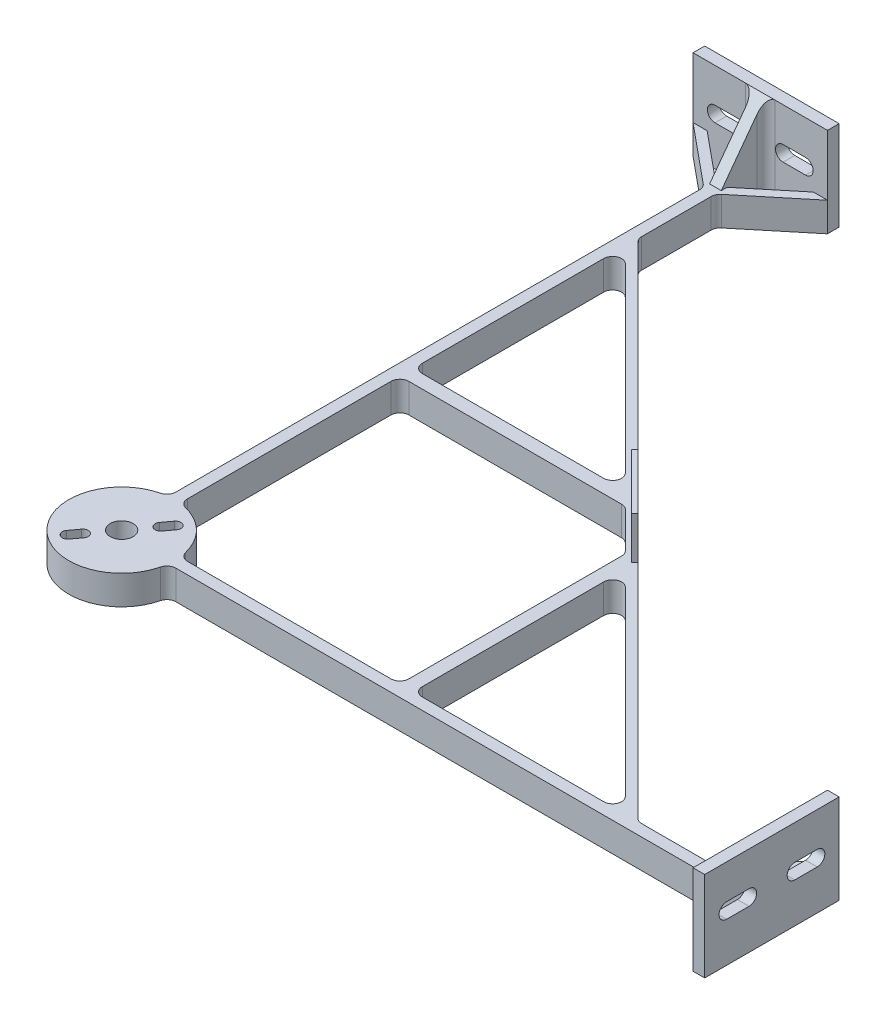
SolidWorks part; units mm, degrees
ref_plane "Front Plane" through (0, 0, 0) normal (0, 0, 1) x (1, 0, 0)
ref_plane "Top Plane" through (0, 0, 0) normal (0, 1, 0) x (1, 0, 0)
ref_plane "Right Plane" through (0, 0, 0) normal (1, 0, 0) x (0, 0, -1)
sketch "Sketch1" plane through (0, 0, 0) normal (0, 1, 0) x (1, 0, 0)
  line L0 (1.651, 14.8948) -> (1.651, 77.2021)
  line L1 (0, 0) -> (0, 189.2633) construction
  line L2 (-1.651, 14.8948) -> (-1.651, 180.975)
  line L3 (-1.651, 180.975) -> (1.651, 180.975)
  line L4 (-12.33, -16.663) -> (12.0176, 16.2408) construction
  line L5 (14.8948, -1.651) -> (180.975, -1.651)
  line L6 (4.6836, 6.3296) -> (6.4967, 8.7797) construction
  line L7 (3.4586, 7.2361) -> (5.2716, 9.6862)
  line L8 (180.975, -1.651) -> (180.975, 1.651)
  line L9 (14.8948, 1.651) -> (141.0789, 1.651)
  line L10 (5.9087, 5.4231) -> (7.7217, 7.8732)
  line L11 (0, 0) -> (16.238, -12.0155) construction
  line L12 (-4.6836, -6.3296) -> (-6.4967, -8.7797) construction
  line L13 (-5.9087, -5.4231) -> (-7.7217, -7.8732)
  line L14 (-3.4586, -7.2361) -> (-5.2716, -9.6862)
  line L15 (-1.651, 14.8948) -> (14.8948, -1.651) construction
  line L16 (1.651, 141.0789) -> (61.7178, 81.0121)
  line L17 (144.6711, 1.651) -> (1.651, 144.6711)
  line L18 (144.6711, 1.651) -> (166.629, 1.651)
  line L19 (141.0789, 1.651) -> (144.6711, 1.651) construction
  line L20 (1.651, 144.6711) -> (1.651, 180.975)
  line L21 (1.651, 81.0121) -> (61.7178, 81.0121)
  line L22 (1.651, 77.2021) -> (65.5278, 77.2021)
  line L23 (0, 0) -> (69.7604, 69.7604) construction
  line L24 (77.2021, 1.651) -> (77.2021, 65.5278)
  line L25 (81.0121, 1.651) -> (81.0121, 61.7178)
  line L26 (81.0121, 61.7178) -> (141.0789, 1.651)
  line L27 (65.5278, 77.2021) -> (77.2021, 65.5278)
  line L28 (1.651, 81.0121) -> (1.651, 141.0789)
  line L29 (169.921, 1.651) -> (180.975, 15.0573)
  line L30 (180.975, 15.0573) -> (180.975, 19.05)
  line L31 (180.975, 19.05) -> (166.629, 1.651)
  line L32 (166.4345, 0) -> (201.9953, 0) construction
  line L33 (180.975, -19.05) -> (166.629, -1.651)
  line L34 (180.975, -15.0573) -> (180.975, -19.05)
  line L35 (169.921, -1.651) -> (180.975, -15.0573)
  line L36 (169.921, 1.651) -> (180.975, 1.651)
  line L37 (166.629, 1.651) -> (169.921, 1.651) construction
  line L38 (-15.0573, 180.975) -> (-19.05, 180.975)
  line L39 (-19.05, 180.975) -> (-1.651, 166.629)
  line L40 (-1.651, 169.921) -> (-15.0573, 180.975)
  line L41 (1.651, 169.921) -> (15.0573, 180.975)
  line L42 (15.0573, 180.975) -> (19.05, 180.975)
  line L43 (19.05, 180.975) -> (1.651, 166.629)
  arc A0 (14.8948, 1.651) -> (1.651, 14.8948) centre (0, 0) ccw
  circle A1 centre (0, 0) radius 3.2385
  arc A2 (3.4586, 7.2361) -> (5.9087, 5.4231) centre (4.6836, 6.3296) ccw
  arc A3 (7.7217, 7.8732) -> (5.2716, 9.6862) centre (6.4967, 8.7797) ccw
  arc A4 (-5.9087, -5.4231) -> (-3.4586, -7.2361) centre (-4.6836, -6.3296) cw
  arc A5 (-5.2716, -9.6862) -> (-7.7217, -7.8732) centre (-6.4967, -8.7797) cw
  arc A6 (-1.651, 14.8948) -> (14.8948, -1.651) centre (0, 0) ccw
  point P14 (5.5901, 7.5546)
  point P25 (-5.5901, -7.5546)
  point P34 (142.875, 1.651)
  point P53 (168.275, 1.651)
  dimension "D3" = 29.972
  dimension "D1" = 6.477
  dimension "D6" = 1.524
  dimension "D7" = 3.048
  dimension "D2" = 36.5
  dimension "D4" = 3.302
  dimension "D5" = 3.302
  dimension "D8" = 7.874
  dimension "D9" = 2.54
  dimension "D10" = 38.1
  dimension "D11" = 3.81
  dimension "D12" = 16.51
  dimension "D13" = 38.1
  dimension "D14" = 12.7
  dimension "D15" = 2.54
  dimension "D16" = 180.975
  dimension "D17" = 180.975
extrude "Boss-Extrude1" add sketch "Sketch1" along normal blind 8.255 contours L2 A6 L5 L8 L36 L29 L30 L31 L18 L17 L20 L3 L14 A5 L13 A4 L9 A0 L0 L22 L27 L24 L25 L26 L21 L28 L16 A1 A3 L10 A2 L7 | L35 L5 L33 L34 | L2 L40 L38 L39 | L43 L42 L41 L20 region at (1.1203, 0, -90.7619) region at (-9.3955, 0, -174.5894) region at (174.5894, 0, 9.3955) region at (9.3955, 0, -174.5894)
sketch "Sketch3" plane through (0, 0, 0) normal (0, 1, 0) x (1, 0, 0)
  line L0 (0, 0) -> (128.7769, 128.7769) construction
  line L1 (180.975, 19.05) -> (184.277, 19.05)
  line L2 (180.975, 19.05) -> (180.975, -19.05)
  line L3 (180.975, -19.05) -> (184.277, -19.05)
  line L4 (184.277, 19.05) -> (184.277, -19.05)
  line L5 (19.05, 184.277) -> (-19.05, 184.277)
  line L6 (-19.05, 180.975) -> (-19.05, 184.277)
  line L7 (19.05, 180.975) -> (-19.05, 180.975)
  line L8 (19.05, 180.975) -> (19.05, 184.277)
  dimension "D1" = 3.302
extrude "Boss-Extrude3" add sketch "Sketch3" along normal blind 25.4
sketch "Sketch4" plane through (0, 8.255, 0) normal (0, 1, 0) x (1, 0, 0)
  line L0 (65.2584, 81.0637) -> (64.3604, 80.1656)
  line L1 (144.6711, 1.651) -> (1.651, 144.6711) construction
  line L2 (64.3604, 80.1656) -> (80.1656, 64.3604)
  line L3 (80.1656, 64.3604) -> (81.0637, 65.2584)
  line L4 (81.0637, 65.2584) -> (65.2584, 81.0637)
  line L5 (71.365, 71.365) -> (72.263, 72.263) construction
  line L6 (65.5278, 77.2021) -> (77.2021, 65.5278) construction
  dimension "D1" = 22.352
  dimension "D2" = 1.27
extrude "Boss-Extrude4" add sketch "Sketch4" along normal blind 11.938
sketch "Sketch5" plane through (184.277, 0, 0) normal (1, 0, 0) x (0, 0, -1)
  line L0 (-12.827, 13.4726) -> (-6.477, 13.4726) construction
  line L1 (-12.827, 15.6316) -> (-6.477, 15.6316)
  line L2 (-12.827, 11.3136) -> (-6.477, 11.3136)
  line L3 (0, 4.9298) -> (0, 30.0782) construction
  line L4 (12.827, 13.4726) -> (6.477, 13.4726) construction
  line L5 (12.827, 15.6316) -> (6.477, 15.6316)
  line L6 (12.827, 11.3136) -> (6.477, 11.3136)
  arc A0 (-12.827, 15.6316) -> (-12.827, 11.3136) centre (-12.827, 13.4726) ccw
  arc A1 (-6.477, 11.3136) -> (-6.477, 15.6316) centre (-6.477, 13.4726) ccw
  arc A2 (12.827, 15.6316) -> (12.827, 11.3136) centre (12.827, 13.4726) cw
  arc A3 (6.477, 11.3136) -> (6.477, 15.6316) centre (6.477, 13.4726) cw
  point P2 (-9.652, 13.4726)
  point P12 (9.652, 13.4726)
  dimension "D1" = 6.35
  dimension "D2" = 4.318
  dimension "D3" = 9.652
ref_plane "Plane1" through (0, 0, 0) normal (0.7071, 0, 0.7071) x (0.7071, 0, -0.7071)
extrude "Cut-Extrude1" cut sketch "Sketch5" against normal through all
mirror "Mirror1" about plane through (0, 0, 0) normal (0.7071, 0, 0.7071) of "Cut-Extrude1"
sketch "Sketch6" plane through (0, 0, 0) normal (0, 1, 0) x (1, 0, 0)
  line L0 (169.921, 1.651) -> (180.975, 1.651) construction
  line L1 (180.975, -1.651) -> (168.275, -1.651)
  line L2 (180.975, -1.651) -> (180.975, 1.651)
  line L3 (180.975, 1.651) -> (168.275, 1.651)
  line L4 (168.275, -1.651) -> (168.275, 1.651)
  dimension "D1" = 12.7
extrude "Boss-Extrude5" add sketch "Sketch6" along normal blind 25.4
sketch "Sketch7" plane through (0, 0, -1.651) normal (0, 0, -1) x (-1, 0, 0)
  line L0 (-180.975, 25.4) -> (-168.275, 8.255)
  line L1 (-168.275, 8.255) -> (-168.275, 25.4)
  line L2 (-168.275, 25.4) -> (-180.975, 25.4)
extrude "Cut-Extrude2" cut sketch "Sketch7" against normal blind 25.4
sketch "Sketch8" plane through (0, 0, 0) normal (0, 1, 0) x (1, 0, 0)
  line L0 (1.651, 169.921) -> (1.651, 180.975) construction
  line L1 (-1.651, 180.975) -> (1.651, 180.975)
  line L2 (-1.651, 180.975) -> (-1.651, 168.275)
  line L3 (-1.651, 168.275) -> (1.651, 168.275)
  line L4 (1.651, 180.975) -> (1.651, 168.275)
  dimension "D1" = 12.7
extrude "Boss-Extrude6" add sketch "Sketch8" along normal blind 25.4
sketch "Sketch9" plane through (1.651, 0, 0) normal (1, 0, 0) x (0, 0, -1)
  line L0 (180.975, 25.4) -> (168.275, 8.255)
  line L1 (168.275, 8.255) -> (168.275, 25.4)
  line L2 (168.275, 25.4) -> (180.975, 25.4)
extrude "Cut-Extrude3" cut sketch "Sketch9" against normal blind 25.4
fillet "Fillet1" radius 2.54 24 edges at (180.975, 12.7, 1.651) (-1.651, 12.7, -180.975) (141.0789, 4.1275, -1.651) (61.7178, 4.1275, -81.0121) (1.651, 4.1275, -141.0789) (81.0121, 4.1275, -61.7178) (14.8948, 4.1275, 1.651) (-1.651, 4.1275, -14.8948) (180.975, 12.7, -1.651) (77.2021, 4.1275, -1.651) (1.651, 12.7, -180.975) (1.651, 4.1275, -77.2021) (166.629, 4.1275, 1.651) (65.5278, 4.1275, -77.2021) (-1.651, 4.1275, -166.629) (77.2021, 4.1275, -65.5278) (1.651, 4.1275, -166.629) (1.651, 4.1275, -14.8948) (1.651, 4.1275, -144.6711) (1.651, 4.1275, -81.0121) (81.0121, 4.1275, -1.651) (166.629, 4.1275, -1.651) (14.8948, 4.1275, -1.651) (144.6711, 4.1275, -1.651)
